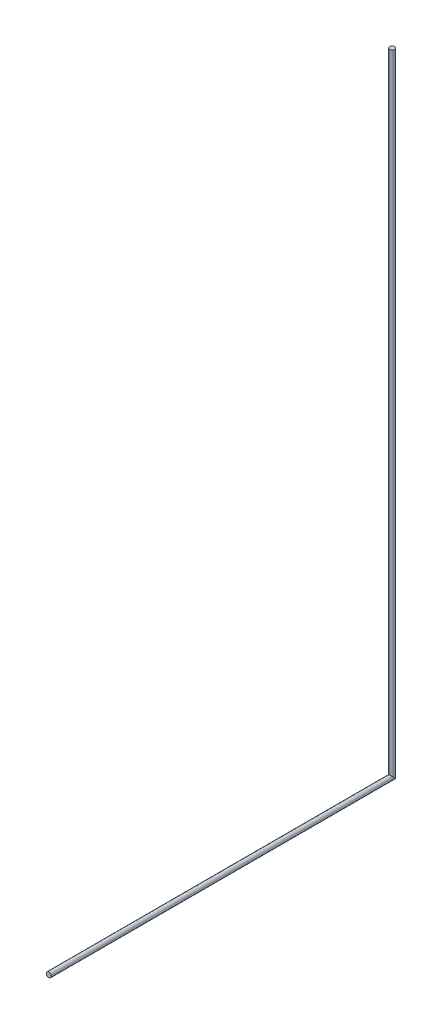
SolidWorks part; units mm, degrees
ref_plane "Спереди" through (0, 0, 0) normal (0, 0, 1) x (1, 0, 0)
ref_plane "Сверху" through (0, 0, 0) normal (0, 1, 0) x (1, 0, 0)
ref_plane "Справа" through (0, 0, 0) normal (1, 0, 0) x (0, 0, -1)
sketch "Эскиз1" plane through (0, 0, 0) normal (0, 1, 0) x (1, 0, 0)
  circle A0 centre (0, 0) radius 4
  dimension "D1" = 8
extrude "Бобышка-Вытянуть1" add sketch "Эскиз1" along normal blind 1015
sketch "Эскиз2" plane through (0, 0, 0) normal (0, 0, 1) x (1, 0, 0)
  circle A0 centre (0, 0) radius 4
extrude "Бобышка-Вытянуть2" add sketch "Эскиз2" along normal blind 552.5
fillet "Скругление1" radius 13 1 edges at (0, 0, 0)
